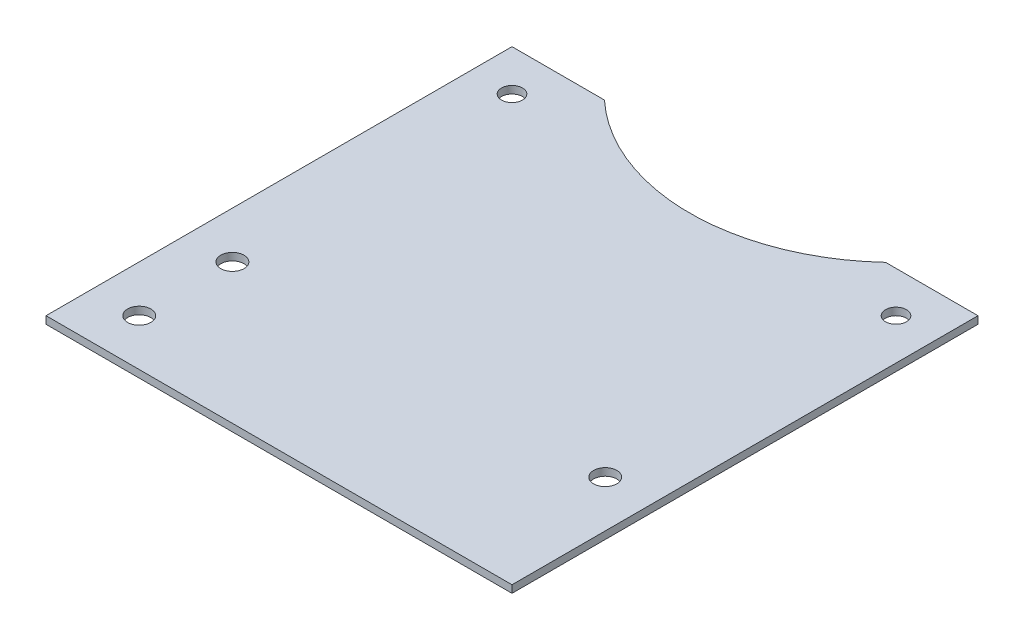
SolidWorks part; units mm, degrees
ref_plane "Front Plane" through (0, 0, 0) normal (0, 0, 1) x (1, 0, 0)
ref_plane "Top Plane" through (0, 0, 0) normal (0, 1, 0) x (1, 0, 0)
ref_plane "Right Plane" through (0, 0, 0) normal (1, 0, 0) x (0, 0, -1)
sketch "Sketch1" plane through (0, 0, 0) normal (0, 1, 0) x (1, 0, 0)
  line L0 (-40, -40) -> (-40, -20) construction
  line L1 (-50, -50) -> (50, -50)
  line L2 (-50, -50) -> (-50, 50)
  line L3 (-50, 50) -> (50, 50)
  line L4 (50, -50) -> (50, 50)
  line L5 (-50, -50) -> (50, 50) construction
  line L6 (-50, 50) -> (50, -50) construction
  line L7 (-40, -20) -> (40, -20) construction
  line L8 (-41.2, 41.2) -> (41.2, 41.2) construction
  circle A0 centre (-40, -40) radius 2.5
  circle A1 centre (-40, -20) radius 2.5
  circle A2 centre (40, -20) radius 2.5
  circle A3 centre (-41.2, 41.2) radius 2.25
  circle A4 centre (41.2, 41.2) radius 2.25
  point P0 (0, 0)
  point P8 (0, -20)
  dimension "D3" = 5
  dimension "D6" = 4.5
  dimension "D1" = 100
  dimension "D2" = 10
  dimension "D4" = 20
  dimension "D5" = 82.4
extrude "Boss-Extrude1" add sketch "Sketch1" along normal mid plane 1.6
ref_axis "Axis1" through (-40, 0.8, 20) along (0, -1, 0)
ref_axis "Axis2" through (40, 0.8, 20) along (0, -1, 0)
ref_plane "Plane1" through (0, 0, 20) normal (0, 0, -1) x (-1, 0, 0)
sketch "Sketch2" plane through (0, 0.8, 0) normal (0, 1, 0) x (1, 0, 0)
  line L0 (50, 50) -> (-50, 50) construction
  circle A0 centre (0, 82.44) radius 44.3
  point P2 (0, 0)
  point P4 (0, 81.4907)
  dimension "D1" = 88.6
  dimension "D2" = 32.44
extrude "Cut-Extrude1" cut sketch "Sketch2" against normal through all
